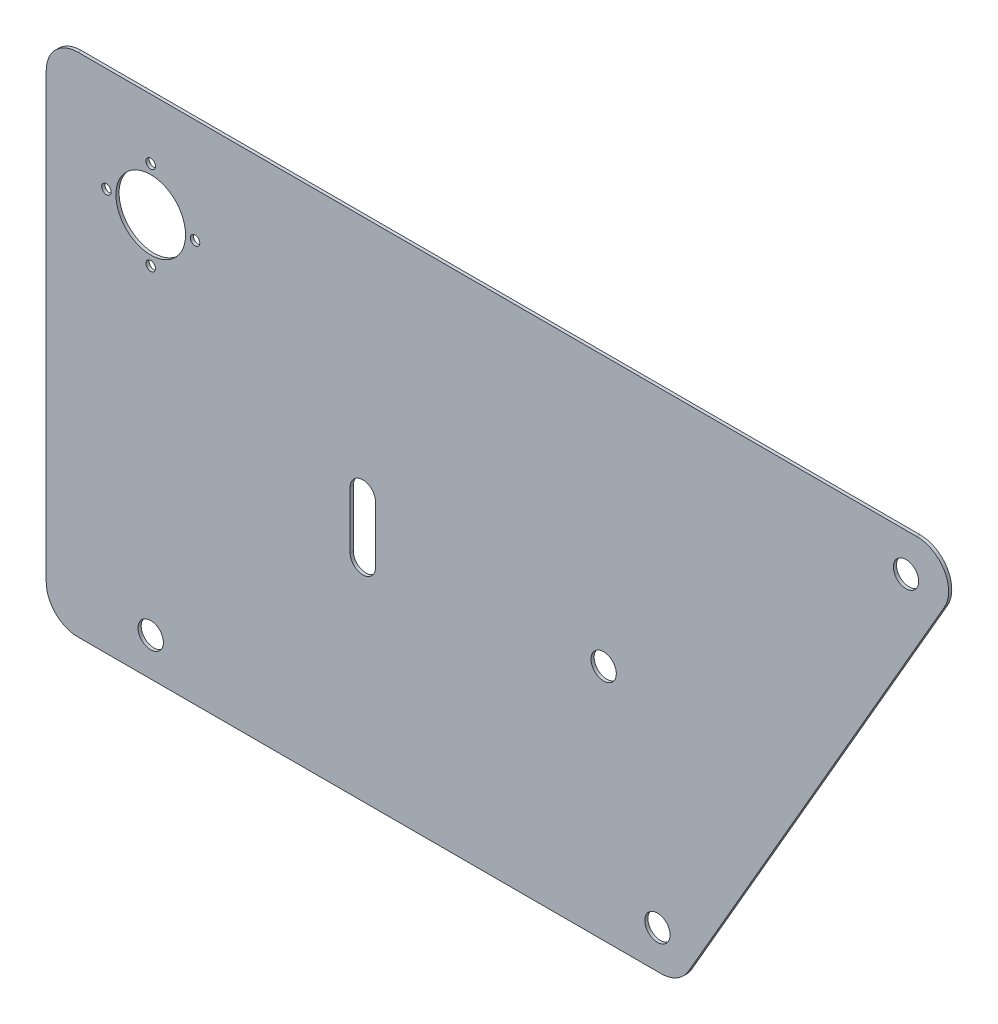
SolidWorks part; units mm, degrees
ref_plane "Front Plane" through (0, 0, 0) normal (0, 0, 1) x (1, 0, 0)
ref_plane "Top Plane" through (0, 0, 0) normal (0, 1, 0) x (1, 0, 0)
ref_plane "Right Plane" through (0, 0, 0) normal (1, 0, 0) x (0, 0, -1)
sketch "Sketch1" plane through (0, 0, 0) normal (0, 0, 1) x (1, 0, 0)
  line L0 (100, 80) -> (192.376, 80)
  line L1 (-100, -80) -> (100, -80)
  line L2 (-100, -80) -> (-100, 80)
  line L3 (-100, 80) -> (100, 80)
  line L4 (100, -80) -> (100, 80)
  line L5 (-100, -80) -> (100, 80) construction
  line L6 (-100, 80) -> (100, -80) construction
  line L7 (192.376, 80) -> (100, -80)
  line L8 (100, 80) -> (100, -80)
  point P0 (0, 0)
  dimension "D1" = 160
  dimension "D2" = 200
  dimension "D3" = 30
extrude "Boss-Extrude1" add sketch "Sketch1" along normal blind 1 contours L1 L4 L3 L2 | L7 L0 L4 region at (0, 0, 0) region at (130.792, 26.6667, 0)
fillet "Fillet1" radius 10 4 edges at (192.376, 80, 0.5) (100, -80, 0.5) (-100, -80, 0.5) (-100, 80, 0.5)
sketch "Sketch2" plane through (0, 0, 1) normal (0, 0, 1) x (1, 0, 0)
  line L0 (-90, -80) -> (94.2265, -80) construction
  line L1 (183.7158, 65) -> (102.8868, -75) construction
  line L2 (-90, 80) -> (175.0555, 80) construction
  line L3 (-100, -70) -> (-100, 70) construction
  line L4 (0, -14) -> (0, 4) construction
  line L5 (-4, -14) -> (-4, 4)
  line L6 (4, -14) -> (4, 4)
  line L8 (0, -0.55) -> (0, 0.55) construction
  circle A0 centre (93.0718, -68) radius 4
  circle A1 centre (171.5914, 68) radius 4
  circle A2 centre (-67, 47) radius 11
  circle A3 centre (-67, -68) radius 4
  circle A4 centre (-53, 47) radius 1.5
  circle A5 centre (-67, 61) radius 1.5
  circle A6 centre (-81, 47) radius 1.5
  circle A7 centre (-67, 33) radius 1.5
  arc A8 (-4, -14) -> (4, -14) centre (0, -14) ccw
  arc A9 (4, 4) -> (-4, 4) centre (0, 4) ccw
  circle A10 centre (76.0815, -5) radius 4
  point P24 (0, -5)
  point P31 (76.0815, -8.9467)
  point P32 (0, -8.9467)
  point P37 (0, 0)
  point P38 (0, 0)
  dimension "D3" = 8
  dimension "D4" = 8
  dimension "D9" = 22
  dimension "D10" = 8
  dimension "D12" = 3
  dimension "D13" = 3
  dimension "D14" = 3
  dimension "D15" = 3
  dimension "D16" = 14
  dimension "D20" = 4
  dimension "D22" = 8
  dimension "D1" = 12
  dimension "D2" = 12
  dimension "D5" = 12
  dimension "D6" = 12
  dimension "D7" = 33
  dimension "D8" = 33
  dimension "D11" = 12
  dimension "D17" = 14
  dimension "D18" = 14
  dimension "D19" = 14
  dimension "D21" = 18
  dimension "D23" = 85
  dimension "D24" = 85
extrude "Cut-Extrude1" cut sketch "Sketch2" against normal blind 3
